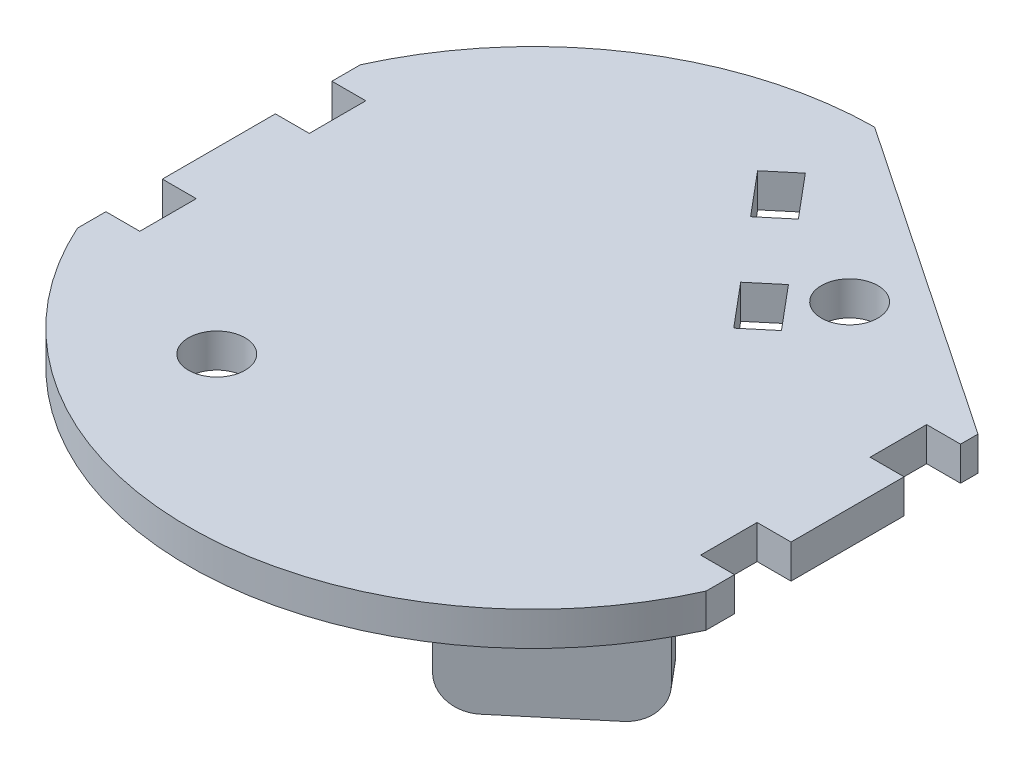
SolidWorks part; units mm, degrees
ref_plane "Alzado" through (0, 0, 0) normal (0, 0, 1) x (1, 0, 0)
ref_plane "Planta" through (0, 0, 0) normal (0, 1, 0) x (1, 0, 0)
ref_plane "Vista lateral" through (0, 0, 0) normal (1, 0, 0) x (0, 0, -1)
sketch "Croquis1" plane through (0, 0, 0) normal (0, 1, 0) x (1, 0, 0)
  circle A0 centre (0, 0) radius 30.5
extrude "Saliente-Extruir1" add sketch "Croquis1" along normal blind 3
sketch "Croquis5" plane through (0, 3, 0) normal (0, 1, 0) x (1, 0, 0)
  line L0 (0, 0) -> (0, 10)
  line L1 (28.8141, -5) -> (30.0874, -5)
  line L2 (28.8141, 5) -> (30.0874, 5)
  line L3 (-24.8141, 10) -> (-28.8141, 10)
  line L4 (24.8141, -5) -> (24.8141, -10)
  line L5 (-24.8141, -10) -> (-28.8141, -10)
  line L6 (24.8141, -5) -> (28.8141, -5)
  line L7 (24.8141, 5) -> (24.8141, 10)
  line L8 (-24.8141, 5) -> (-28.8141, 5)
  line L9 (-24.8141, 5) -> (-24.8141, 10)
  line L10 (-24.8141, -5) -> (-28.8141, -5)
  line L11 (-24.8141, -5) -> (-24.8141, -10)
  line L12 (24.8141, 5) -> (28.8141, 5)
  line L13 (24.8141, -10) -> (28.8141, -10)
  line L14 (24.8141, 10) -> (28.8141, 10)
  line L15 (-28.8141, 5) -> (-30.0874, 5)
  line L16 (-28.8141, -5) -> (-30.0874, -5)
  circle A1 centre (0, 0) radius 30.5 construction
  arc A2 (-28.8141, 10) -> (-30.0874, 5) centre (0, 0) ccw
  arc A3 (28.8141, 10) -> (28.8141, -10) centre (0, 0) cw
  arc A4 (-30.0874, -5) -> (-28.8141, -10) centre (0, 0) ccw
  arc A5 (30.0874, -5) -> (28.8141, -10) centre (0, 0) cw
  arc A6 (28.8141, 10) -> (30.0874, 5) centre (0, 0) cw
  circle M2 centre (0, 0) radius 30.5
extrude "Cortar-Extruir3" cut sketch "Croquis5" against normal blind 4 contours L11 L10 L8 L9 L3 L5 M2 | L15 L8 L9 L3 M2 | L14 L7 L12 L2 M2 | L4 L13 L1 L6 M2 region at (27.1844, 3, 7.3876) region at (27.1844, 3, -7.3876) region at (-27.1844, 3, 7.3876) region at (-27.1844, 3, -7.3876)
sketch "Croquis9" plane through (0, 3, 0) normal (0, 1, 0) x (1, 0, 0)
  line L0 (5.6733, 12.6854) -> (8.8872, 8.8552)
  line L2 (7.9714, 14.6138) -> (11.1854, 10.7835)
  line L3 (-24.8141, -5) -> (-24.8141, -10)
  line L4 (-24.8141, -10) -> (-28.8141, -10)
  line L5 (11.1854, 10.7835) -> (8.8872, 8.8552)
  line L7 (7.9714, 14.6138) -> (5.6733, 12.6854)
  line L11 (-2.1205, 21.9737) -> (1.0934, 18.1435)
  line L12 (0.1776, 23.902) -> (3.3916, 20.0718)
  line L13 (-24.8141, 10) -> (-28.8141, 10)
  line L14 (3.3916, 20.0718) -> (1.0934, 18.1435)
  line L15 (0.1776, 23.902) -> (-2.1205, 21.9737)
  arc A1 (28.8141, 10) -> (-28.8141, 10) centre (0, 0) ccw construction
  arc A5 (-28.8141, -10) -> (28.8141, -10) centre (0, 0) ccw construction
  arc A7 (-28.8141, -10) -> (22.3289, -20.7766) centre (0, 0) ccw
  arc A8 (-28.8141, 10) -> (-8.3073, 29.3469) centre (0, 0) cw
extrude "Cortar-Extruir6" cut sketch "Croquis9" against normal blind 10 contours L2 L7 | L12 L15 L14 region at (8.4293, 3, -11.7345) region at (0.6355, 3, -21.0227)
sketch "Croquis10" plane through (0, 3, 0) normal (0, 1, 0) x (1, 0, 0)
  line L0 (0, 0) -> (12, 0)
  line L1 (12, 0) -> (12, 16)
  line L2 (0, 0) -> (-12, 0)
  line L3 (-12, 0) -> (-12, -16)
  circle A0 centre (12, 16) radius 2.5
  circle A1 centre (-12, -16) radius 2.5
extrude "Cortar-Extruir7" cut sketch "Croquis10" against normal blind 10 contours A0 | A1 region at (10.2822, 3, -17.7178) region at (-10.2822, 3, 14.2822)
sketch "Croquis11" plane through (0, 3, 0) normal (0, 1, 0) x (1, 0, 0)
  line L0 (27.8141, 5) -> (30.0874, 5)
  line L1 (-27.8141, 5) -> (-27.8141, -5)
  line L2 (-24.8141, -5) -> (-30.0874, -5) construction
  line L3 (27.8141, 10) -> (28.8141, 10)
  line L4 (24.8141, 5) -> (30.0874, 5) construction
  line L5 (27.8141, 5) -> (27.8141, -5)
  line L6 (24.8141, -5) -> (30.0874, -5) construction
  line L7 (27.8141, -5) -> (30.0874, -5)
  line L8 (24.8141, 10) -> (28.8141, 10) construction
  line L9 (27.8141, 10) -> (27.8141, 12.5151)
  line L10 (27.8141, -10) -> (28.8141, -10)
  line L11 (24.8141, -10) -> (28.8141, -10) construction
  line L12 (27.8141, -10) -> (27.8141, -12.5151)
  line L13 (-28.8141, -10) -> (-27.8141, -10)
  line L14 (-24.8141, 10) -> (-28.8141, 10) construction
  line L15 (-27.8141, 10) -> (-27.8141, 12.5151)
  line L16 (-27.8141, -5) -> (-30.0874, -5)
  line L17 (-27.8141, -10) -> (-27.8141, -12.5151)
  line L18 (-27.8141, 10) -> (-28.8141, 10)
  line L19 (-30.0874, 5) -> (-27.8141, 5)
  arc A0 (28.8141, 10) -> (-28.8141, 10) centre (0, 0) ccw construction
  arc A1 (-28.8141, -10) -> (28.8141, -10) centre (0, 0) ccw construction
  arc A2 (28.8141, 10) -> (-28.8141, 10) centre (0, 0) ccw construction
  arc A3 (30.0874, -5) -> (30.0874, 5) centre (0, 0) ccw
  arc A4 (28.8141, -10) -> (27.8141, -12.5151) centre (0, 0) cw
  arc A5 (28.8141, 10) -> (27.8141, 12.5151) centre (0, 0) ccw
  arc A6 (-30.0874, -5) -> (-30.0874, 5) centre (0, 0) cw
  arc A7 (-27.8141, 12.5151) -> (-28.8141, 10) centre (0, 0) ccw
  arc A8 (-28.8141, -10) -> (-27.8141, -12.5151) centre (0, 0) ccw
  arc M11 (28.8141, 10) -> (-28.8141, 10) centre (0, 0) ccw
  line M17 (-24.8141, 5) -> (-30.0874, 5)
  arc M18 (-30.0874, 5) -> (-30.0874, -5) centre (0, 0) ccw
  line M19 (-30.0874, -5) -> (-24.8141, -5)
  arc M21 (-28.8141, -10) -> (28.8141, -10) centre (0, 0) ccw
  line M22 (28.8141, -10) -> (24.8141, -10)
  line M24 (24.8141, -5) -> (30.0874, -5)
  arc M25 (30.0874, -5) -> (30.0874, 5) centre (0, 0) ccw
  line M26 (30.0874, 5) -> (24.8141, 5)
  line M28 (24.8141, 10) -> (28.8141, 10)
  line M54 (-24.8141, -10) -> (-28.8141, -10)
  line M56 (-28.8141, 10) -> (-24.8141, 10)
extrude "Cortar-Extruir8" cut sketch "Croquis11" against normal blind 3 contours L17 M54 M21 | L1 M17 M18 M19 | L15 M56 M11 | L12 M22 M21 | L5 M26 M24 M25 | L9 M28 M11 region at (29.0914, 3, 0) region at (-29.0914, 3, 0) region at (28.1547, 3, -10.8559) region at (-28.1547, 3, -10.8559) region at (-28.1547, 3, 10.8559) region at (28.1547, 3, 10.8559)
sketch "Croquis13" plane through (0, 0, 0) normal (0, -1, 0) x (1, 0, 0)
  line L0 (-6.8167, 4.322) -> (-19.6724, -10.9989)
  line L1 (-19.6724, -10.9989) -> (-17.3743, -12.9273)
  line L2 (-17.3743, -12.9273) -> (-4.5186, 2.3936)
  line L3 (-4.5186, 2.3936) -> (-6.8167, 4.322)
  line L4 (21.5273, 8.9312) -> (23.4556, 11.2293)
  line L5 (23.4556, 11.2293) -> (11.965, 20.8711)
  line L6 (11.965, 20.8711) -> (10.0366, 18.573)
  line L7 (10.0366, 18.573) -> (21.5273, 8.9312)
extrude "Saliente-Extruir2" add sketch "Croquis13" along normal blind 10
fillet "Redondeo1" radius 3 4 edges at (11.0008, -10, 19.7221) (22.4915, -10, 10.0802) (-5.6676, -10, 3.3578) (-18.5234, -10, -11.9631)
fillet "Redondeo2" radius 1 6 edges at (17.7103, 0, 16.0502) (11.0008, 0, 19.7221) (-5.6676, 0, 3.3578) (-13.2446, 0, -3.3385) (22.4915, 0, 10.0802) (-18.5234, 0, -11.9631)
sketch "Croquis14" plane through (0, 3, 0) normal (0, 1, 0) x (1, 0, 0)
  line L3 (29.8013, 10.2046) -> (-1.7022, 31.454)
  circle A0 centre (0, 0) radius 31.5
  line M12 (27.8141, 10) -> (27.8141, 12.5151)
  arc M13 (27.8141, 12.5151) -> (-27.8141, 12.5151) centre (0, 0) ccw
extrude "Cortar-Extruir9" cut sketch "Croquis14" against normal blind 3 contours L3 M12 M13 region at (15.2326, 3, -22.6507)
